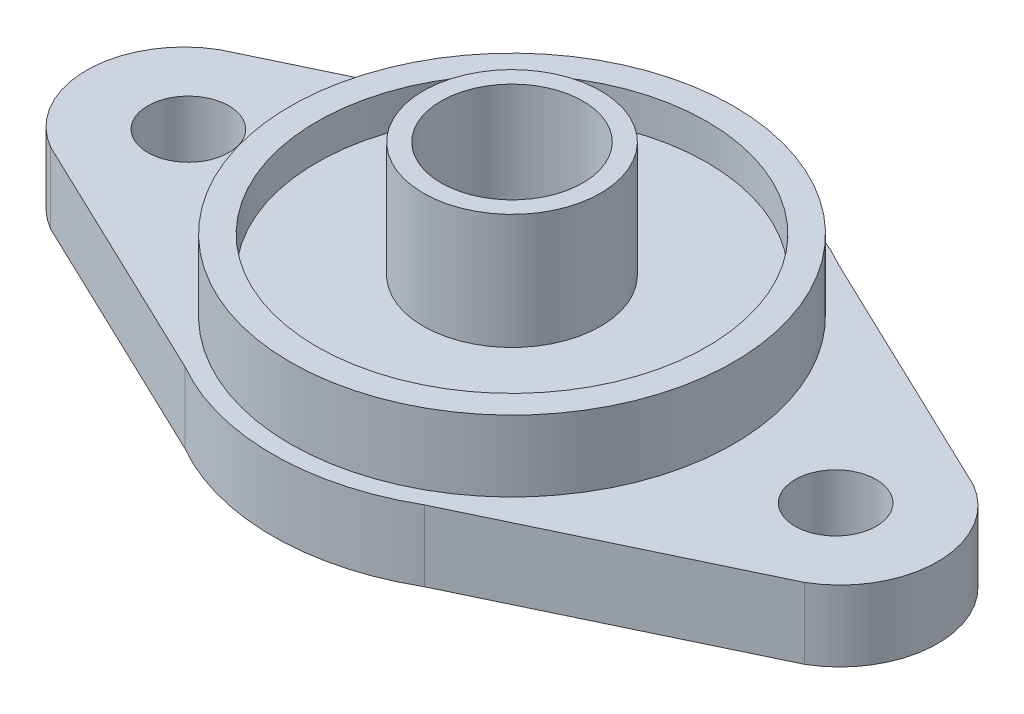
SolidWorks part; units mm, degrees
ref_plane "Front Plane" through (0, 0, 0) normal (0, 0, 1) x (1, 0, 0)
ref_plane "Top Plane" through (0, 0, 0) normal (0, 1, 0) x (1, 0, 0)
ref_plane "Right Plane" through (0, 0, 0) normal (1, 0, 0) x (0, 0, -1)
sketch "Sketch1" plane through (0, 0, 0) normal (0, 1, 0) x (1, 0, 0)
  line L0 (-24, 0) -> (24, 0) construction
  line L1 (0, 0) -> (0, 13.5)
  line L2 (0, 0) -> (-6.75, 11.6913) construction
  line L3 (-21.25, 4.7631) -> (-6.75, 11.6913)
  line L4 (0, 0) -> (6.75, 11.6913) construction
  line L5 (6.75, 11.6913) -> (21.25, 4.7631)
  line L6 (6.75, -11.6913) -> (21.25, -4.7631)
  line L7 (-21.25, -4.7631) -> (-6.75, -11.6913)
  circle A0 centre (0, 0) radius 4
  circle A1 centre (18.25, 0) radius 2.2859
  circle A2 centre (-18.25, 0) radius 2.2859
  circle A5 centre (0, 0) radius 5
  circle A7 centre (0, 0) radius 12.5
  circle A8 centre (0, 0) radius 11
  circle A9 centre (0, 0) radius 13.5 construction
  circle A10 centre (-18.25, 0) radius 5.6292 construction
  circle A11 centre (18.25, 0) radius 5.6292 construction
  arc A12 (-21.25, -4.7631) -> (-21.25, 4.7631) centre (-18.5, 0) cw
  arc A13 (21.25, -4.7631) -> (21.25, 4.7631) centre (18.5, 0) ccw
  arc A14 (-6.75, 11.6913) -> (6.75, 11.6913) centre (0, 0) cw
  arc A15 (-6.75, -11.6913) -> (6.75, -11.6913) centre (0, 0) ccw
  point P16 (0, 0)
  dimension "D1" = 36.5
  dimension "D3" = 30
  dimension "D4" = 8
  dimension "D2" = 18.25
extrude "Boss-Extrude1" add sketch "Sketch1" along normal blind 4 contours L3 A14 L5 A13 L6 A15 L7 A12
extrude "Boss-Extrude2" add sketch "Sketch1<3>" along normal blind 8 contours A7 | A8
sketch "Sketch1<3>" plane through (0, 0, 0) normal (0, 1, 0) x (1, 0, 0) same geometry as "Sketch1"
extrude "Boss-Extrude3" add sketch "Sketch1<4>" along normal blind 12.5 contours A5 | A0
sketch "Sketch1<4>" plane through (0, 0, 0) normal (0, 1, 0) x (1, 0, 0) same geometry as "Sketch1"
sketch "Sketch3" plane through (0, 4, 0) normal (0, 1, 0) x (1, 0, 0)
  circle A0 centre (0, 0) radius 5
  circle A1 centre (0, 0) radius 11
extrude "Boss-Extrude4" add sketch "Sketch3" along normal blind 2
extrude "Cut-Extrude1" cut sketch "Sketch1<5>" along normal through all contours A2 | A1 | A0
sketch "Sketch1<5>" plane through (0, 0, 0) normal (0, 1, 0) x (1, 0, 0) same geometry as "Sketch1"
